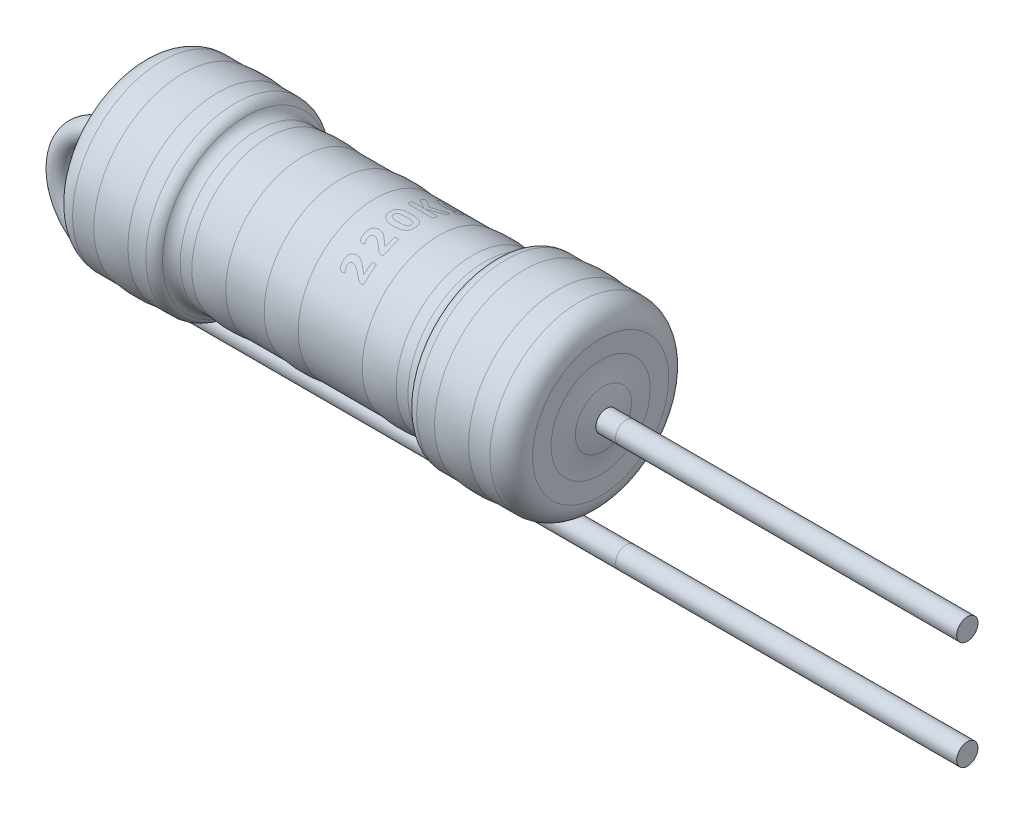
SolidWorks part; units mm, degrees
ref_plane "Front Plane" through (0, 0, 0) normal (0, 0, 1) x (1, 0, 0)
ref_plane "Top Plane" through (0, 0, 0) normal (0, 1, 0) x (1, 0, 0)
ref_plane "Right Plane" through (0, 0, 0) normal (1, 0, 0) x (0, 0, -1)
sketch "Sketch Set Wire Width" plane through (0, 0, 0) normal (0, 0, 1) x (1, 0, 0)
  line L0 (0, 0) -> (6, 0)
  line L1 (6, -2.54) -> (-6, -2.54)
  line L2 (6, 0) -> (14.0102, 0)
  line L3 (-6, 0) -> (-6, -2.54) construction
  line L4 (-6, 0) -> (-6, -2.54) construction
  line L5 (6, -2.54) -> (6, 0) construction
  line L6 (6, -2.54) -> (14.0102, -2.54)
  line L7 (14.0102, -2.54) -> (14.0102, 0) construction
  line L8 (-6, 0) -> (0, 0)
  arc A0 (-6, 0) -> (-6, -2.54) centre (-6, -1.27) ccw
  dimension "D2" = 2.54
  dimension "D3" = 30
  dimension "D1" = 12
  dimension "D4" = 6
sketch "Sketch Wire Diameter" plane through (0, 0, 0) normal (1, 0, 0) x (0, 0, -1)
  circle A0 centre (0, 0) radius 0.25
  dimension "D1" = 0.5
sweep "SET WIRE LENGTH" add profiles "Sketch Wire Diameter" path "Sketch Set Wire Width"
sketch "Sketch3" plane through (0, 0, 0) normal (0, 0, 1) x (1, 0, 0)
  line L0 (-5.4, 0) -> (5.4, 0)
  line L1 (0, 0) -> (0, 1.8) construction
  line L2 (-2.9, 1.8) -> (2.9, 1.8)
  line L3 (-5.4, 0) -> (-5.4, 1.6)
  line L4 (-4.9, 2.1) -> (-3.18, 2.1)
  line L5 (-2.9, 1.82) -> (-2.9, 1.8)
  line L6 (5.4, 0) -> (5.4, 1.6)
  line L7 (4.9, 2.1) -> (3.18, 2.1)
  line L8 (2.9, 1.82) -> (2.9, 1.8)
  arc A0 (-5.4, 1.6) -> (-4.9, 2.1) centre (-4.9, 1.6) cw
  arc A1 (5.4, 1.6) -> (4.9, 2.1) centre (4.9, 1.6) ccw
  arc A2 (-3.18, 2.1) -> (-2.9, 1.82) centre (-3.18, 1.82) cw
  arc A3 (3.18, 2.1) -> (2.9, 1.82) centre (3.18, 1.82) ccw
  dimension "D5" = 0.5
  dimension "D6" = 0.28
  dimension "D1" = 10.8
  dimension "D2" = 5.8
  dimension "D3" = 1.8
  dimension "D4" = 2.1
revolve "Revolve2" add sketch "Sketch3" angle 360 about L0
fillet "Fillet1" radius 0.3 2 edges at (2.9, 0, 1.8) (-2.9, 0, 1.8)
sketch "Sketch5" plane through (0, 0, 0) normal (0, 0, 1) x (1, 0, 0)
  line L0 (0, 0) -> (2, 0) construction
  line L1 (0, 0) -> (-0.3, 0) construction
  line L2 (-0.3, 0) -> (-2, 0) construction
  line L3 (-2, 0) -> (-4, 0) construction
  line L4 (2, 0) -> (4, 0) construction
  line L5 (-4, 0) -> (-4, 2.1) construction
  line L6 (-0.3, 0) -> (-0.3, 1.8) construction
  line L7 (-2, 0) -> (-2, 1.8) construction
  line L8 (2, 0) -> (2, 1.8) construction
  line L9 (4, 0) -> (4, 2.1) construction
  line L10 (-4, 2.1) -> (-4, 2.13) construction
  line L11 (-4.9, 2.1) -> (-3.18, 2.1) construction
  line L12 (4.9, 2.1) -> (3.18, 2.1) construction
  line L13 (-2.9, 1.8) -> (2.9, 1.8) construction
  line L14 (-2, 1.8) -> (-2, 1.83) construction
  line L17 (-4.4, 2.1) -> (-3.6, 2.1)
  line L19 (-5.4, 0) -> (5.4, 0) construction
  line L22 (-2.4, 1.8) -> (-1.6, 1.8) construction
  line L26 (-0.7, 1.8) -> (0.1, 1.8) construction
  line L30 (1.6, 1.8) -> (2.4, 1.8) construction
  line L34 (3.6, 2.1) -> (4.4, 2.1) construction
  line L36 (-0.3, 1.8) -> (-0.3, 1.83) construction
  line L37 (2, 1.8) -> (2, 1.83) construction
  line L38 (4, 2.1) -> (4, 2.13) construction
  arc A0 (-4.4, 2.1) -> (-3.6, 2.1) centre (-4, -0.5517) cw
  arc A1 (-2.4, 1.8) -> (-1.6, 1.8) centre (-2, -0.8517) cw construction
  arc A2 (-0.7, 1.8) -> (0.1, 1.8) centre (-0.3, -0.8517) cw construction
  arc A3 (1.6, 1.8) -> (2.4, 1.8) centre (2, -0.8517) cw construction
  arc A4 (3.6, 2.1) -> (4.4, 2.1) centre (4, -0.5517) cw construction
  dimension "D3" = 0.8
  dimension "D1" = 4
  dimension "D2" = 4
  dimension "D4" = 0.03
  dimension "D5" = 2
  dimension "D6" = 2
  dimension "D7" = 1.7
revolve "Band 1" add sketch "Sketch5" angle 360 about L2
sketch "Sketch8" plane through (0, 0, 0) normal (0, 0, 1) x (1, 0, 0)
  line L0 (-2.4, 1.8) -> (-1.6, 1.8) construction
  line L1 (-2.4, 1.8) -> (-1.6, 1.8)
  arc A0 (-1.6, 1.8) -> (-2.4, 1.8) centre (-2, -0.8517) ccw construction
  arc A1 (-1.6, 1.8) -> (-2.4, 1.8) centre (-2, -0.8517) ccw
revolve "Band 2" add sketch "Sketch8" angle 360 about L2
sketch "Sketch9" plane through (0, 0, 0) normal (0, 0, 1) x (1, 0, 0)
  line L0 (-0.7, 1.8) -> (0.1, 1.8) construction
  line L1 (-0.7, 1.8) -> (0.1, 1.8)
  arc A0 (0.1, 1.8) -> (-0.7, 1.8) centre (-0.3, -0.8517) ccw construction
  arc A1 (0.1, 1.8) -> (-0.7, 1.8) centre (-0.3, -0.8517) ccw
revolve "Band 3" add sketch "Sketch9" angle 360 about L2
sketch "Sketch10" plane through (0, 0, 0) normal (0, 0, 1) x (1, 0, 0)
  line L0 (1.6, 1.8) -> (2.4, 1.8) construction
  line L1 (1.6, 1.8) -> (2.4, 1.8)
  arc A0 (2.4, 1.8) -> (1.6, 1.8) centre (2, -0.8517) ccw construction
  arc A1 (2.4, 1.8) -> (1.6, 1.8) centre (2, -0.8517) ccw
revolve "Band 4" add sketch "Sketch10" angle 360 about L0
sketch "Sketch11" plane through (0, 0, 0) normal (0, 0, 1) x (1, 0, 0)
  line L0 (3.6, 2.1) -> (4.4, 2.1) construction
  line L1 (3.6, 2.1) -> (4.4, 2.1)
  arc A0 (4.4, 2.1) -> (3.6, 2.1) centre (4, -0.5517) ccw construction
  arc A1 (4.4, 2.1) -> (3.6, 2.1) centre (4, -0.5517) ccw
revolve "Band 5" add sketch "Sketch11" angle 360 about L4
sketch "Sketch12" plane through (0, 0, 0) normal (0, 0, 1) x (1, 0, 0)
  line L0 (-5.35, 0) -> (5.35, 0) construction
  line L1 (-5.35, 1) -> (-5.35, 0)
  line L2 (5.35, 1) -> (5.35, 0)
  line L3 (-5.35, 0) -> (-5.55, 0)
  line L4 (5.35, 0) -> (5.55, 0)
  arc A0 (-5.35, 1) -> (-5.55, 0) centre (-2.95, 0) ccw
  arc A1 (5.35, 1) -> (5.55, 0) centre (2.95, 0) cw
  dimension "D3" = 0.2
  dimension "D4" = 2.6
  dimension "D1" = 10.7
  dimension "D2" = 1
revolve "Revolve10" add sketch "Sketch12" angle 360 about L0
fillet "Fillet2" radius 2 2 edges at (5.4, 0, 0.8703) (-5.4, 0, -0.8703)
ref_plane "Plane2" through (0, 3, 0) normal (0, 1, 0) x (1, 0, 0)
sketch "Sketch13" plane through (0, 3, 0) normal (0, 1, 0) x (1, 0, 0)
  line L0 (0, 0) -> (1.15, 0) construction
  line L1 (1.15, 1.75) -> (1.15, -1.75) construction
  text T0 "220KΩ" font "Calibri" height 0.6
  dimension "D1" = 3.5
  dimension "D2" = 1.15
wrap "Wrap1" sketch "Sketch13" wrap type scribe source sketch "Sketch13" face at (0.1, 1.8, 0)
